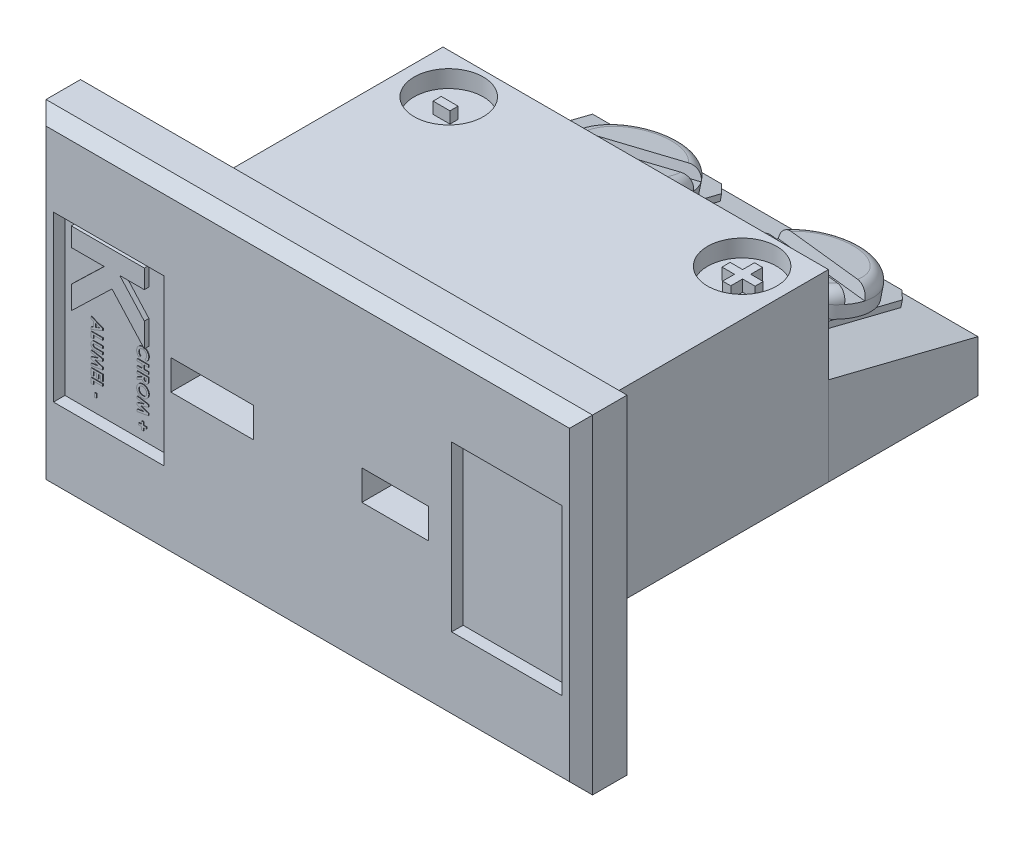
SolidWorks part; units mm, degrees
material "ABS PC"
ref_plane "Front" through (0, 0, 0) normal (0, 0, 1) x (1, 0, 0)
ref_plane "Top" through (0, 0, 0) normal (0, 1, 0) x (1, 0, 0)
ref_plane "Right" through (0, 0, 0) normal (1, 0, 0) x (0, 0, -1)
sketch "Sketch1" plane through (0, 0, 0) normal (0, 0, 1) x (1, 0, 0)
  line L0 (-24.3253, 0) -> (16.3539, 0) construction
  line L1 (-5.95, -0.65) -> (-2.35, -0.65)
  line L2 (-5.95, -0.65) -> (-5.95, 0.65)
  line L3 (-5.95, 0.65) -> (-2.35, 0.65)
  line L4 (-2.35, -0.65) -> (-2.35, 0.65)
  line L5 (2.35, -0.65) -> (5.25, -0.65)
  line L6 (2.35, -0.65) -> (2.35, 0.65)
  line L7 (2.35, 0.65) -> (5.25, 0.65)
  line L8 (5.25, -0.65) -> (5.25, 0.65)
  line L9 (-11.875, 7.15) -> (11.875, 7.15)
  line L10 (-11.875, 7.15) -> (-11.875, -7.15)
  line L11 (-11.875, -7.15) -> (11.875, -7.15)
  line L12 (11.875, 7.15) -> (11.875, -7.15)
  line L13 (0, 12.1646) -> (0, -12.5395) construction
  circle A0 centre (0, 0) radius 10.25 construction
  dimension "D1" = 20.5
  dimension "D2" = 0.65
  dimension "D3" = 1.3
  dimension "D4" = 0.65
  dimension "D5" = 1.3
  dimension "D6" = 2.9
  dimension "D7" = 3.6
  dimension "D8" = 4.7
  dimension "D9" = 2.35
  dimension "D10" = 23.75
  dimension "D11" = 14.3
extrude "Extrude1" add sketch "Sketch1" along normal blind 2
chamfer "Chamfer1" distance 0.5 angle 45 4 edges at (0, -7.15, 2) (11.875, 0, 2) (-11.875, 0, 2) (0, 7.15, 2)
sketch "Sketch2" plane through (0, 0, 2) normal (0, 0, 1) x (1, 0, 0)
  line L0 (-16.3854, 0) -> (14.9768, 0) construction
  line L9 (6.25, 3.575) -> (11.05, 3.575)
  line L10 (6.25, 3.575) -> (6.25, -3.575)
  line L11 (6.25, -3.575) -> (11.05, -3.575)
  line L12 (11.05, 3.575) -> (11.05, -3.575)
  line L13 (0, 8.3719) -> (0, -9.5694) construction
  line L14 (-6.25, -3.575) -> (-11.05, -3.575)
  line L15 (-11.05, 3.575) -> (-11.05, -3.575)
  line L16 (-6.25, 3.575) -> (-11.05, 3.575)
  line L17 (-6.25, 3.575) -> (-6.25, -3.575)
  dimension "D9" = 7.15
  dimension "D10" = 4.8
  dimension "D11" = 6.25
extrude "Cut-Extrude1" cut sketch "Sketch2" against normal blind 0.5
sketch "Sketch3" plane through (0, 0, 0) normal (0, 0, -1) x (-1, 0, 0)
  line L0 (-13.5325, 0) -> (13.4926, 0) construction
  line L1 (0, 8.4341) -> (0, -8.147) construction
  line L2 (-5.25, 0.65) -> (-2.35, 0.65) construction
  line L3 (-5.25, -0.65) -> (-2.35, -0.65)
  line L4 (-5.25, -0.65) -> (-5.25, 0.65)
  line L5 (-5.25, 0.65) -> (-2.35, 0.65)
  line L6 (-2.35, -0.65) -> (-2.35, 0.65)
  line L7 (2.35, -0.65) -> (5.95, -0.65)
  line L8 (2.35, -0.65) -> (2.35, 0.65)
  line L9 (2.35, 0.65) -> (5.95, 0.65)
  line L10 (5.95, -0.65) -> (5.95, 0.65)
  line L11 (-2.35, 0.65) -> (-2.35, -0.65) construction
  line L12 (-5.25, -0.65) -> (-5.25, 0.65) construction
  line L13 (-2.35, -0.65) -> (-5.25, -0.65) construction
  line L14 (2.35, 0.65) -> (5.95, 0.65) construction
  line L15 (5.95, -0.65) -> (2.35, -0.65) construction
  line L16 (2.35, -0.65) -> (2.35, 0.65) construction
  line L17 (5.95, 0.65) -> (5.95, -0.65) construction
  line L19 (-8.375, 4) -> (8.375, 4)
  line L20 (-8.375, 4) -> (-8.375, -4)
  line L21 (-8.375, -4) -> (8.375, -4)
  line L22 (8.375, 4) -> (8.375, -4)
  dimension "D1" = 16.75
  dimension "D2" = 8
extrude "Extrude2" add sketch "Sketch3" along normal blind 12.25
sketch "Sketch4" plane through (4.987, -4.5919, 1.5) normal (0, 0, 1) x (0, -1, 0)
  text T0 "<b>K</b>" font "Century Gothic" height in points 12
extrude "TC Type" add sketch "Sketch4" along normal blind 0.2
sketch "Sketch5" plane through (0, 0, 0) normal (0, 0, -1) x (-1, 0, 0)
  line L0 (5.95, 0.65) -> (5.95, -0.65) construction
  line L1 (5.95, -0.65) -> (2.35, -0.65) construction
  line L3 (-5.25, -0.65) -> (-2.35, -0.65)
  line L4 (-5.25, -0.65) -> (-5.25, -0.15)
  line L5 (-5.25, -0.15) -> (-2.35, -0.15)
  line L6 (-2.35, -0.65) -> (-2.35, -0.15)
  line L8 (2.35, -0.65) -> (5.95, -0.65)
  line L9 (2.35, -0.65) -> (2.35, -0.15)
  line L10 (2.35, -0.15) -> (5.95, -0.15)
  line L11 (5.95, -0.65) -> (5.95, -0.15)
  line L12 (2.35, -0.65) -> (2.35, 0.65) construction
  line L13 (-2.35, 0.65) -> (-2.35, -0.65) construction
  line L14 (-2.35, -0.65) -> (-5.25, -0.65) construction
  line L15 (-5.25, -0.65) -> (-5.25, 0.65) construction
  dimension "D2" = 0.5
  dimension "D3" = 0.5
extrude "Conatcts" add sketch "Sketch5" along normal up to surface (12.25 mm away) separate body up to face at (3.8, 0, -12.25)
sketch "Sketch6" plane through (0, 0, -12.25) normal (0, 0, -1) x (-1, 0, 0)
  line L0 (-8.375, -4) -> (8.375, -4)
  line L1 (-8.375, -0.15) -> (-5.25, -0.15)
  line L2 (-2.35, -0.15) -> (2.35, -0.15)
  line L3 (-5.25, -0.65) -> (-2.35, -0.65)
  line L4 (-5.25, -0.65) -> (-5.25, -0.15)
  line L5 (5.95, -0.15) -> (8.375, -0.15)
  line L6 (-2.35, -0.65) -> (-2.35, -0.15)
  line L7 (2.35, -0.65) -> (5.95, -0.65)
  line L8 (2.35, -0.65) -> (2.35, -0.15)
  line L9 (-2.35, -0.15) -> (-5.25, -0.15) construction
  line L10 (5.95, -0.65) -> (5.95, -0.15)
  line L11 (-5.25, -0.65) -> (-2.35, -0.65) construction
  line L12 (-2.35, -0.65) -> (-2.35, 0.65) construction
  line L13 (-5.25, 0.65) -> (-5.25, -0.65) construction
  line L14 (2.35, -0.65) -> (5.95, -0.65) construction
  line L15 (2.35, 0.65) -> (2.35, -0.65) construction
  line L16 (5.95, -0.65) -> (5.95, 0.65) construction
  line L17 (8.375, -4) -> (8.375, 4) construction
  line L18 (-8.375, 4) -> (-8.375, -4) construction
  line L19 (-8.375, -4) -> (8.375, -4) construction
  line L20 (-8.375, -0.15) -> (-8.375, -4)
  line L21 (8.375, -4) -> (8.375, -0.15)
extrude "Extrude5" add sketch "Sketch6" along normal blind 6.5 separate body
sketch "Sketch7" plane through (0, 0, 0) normal (1, 0, 0) x (0, 0, -1)
  line L1 (12.25, -0.15) -> (20.25, -0.15)
  line L2 (18.75, -0.15) -> (12.25, -0.15) construction
  line L3 (12.25, 4) -> (12.25, -4) construction
  line L4 (20.25, -0.15) -> (20.25, -2.15)
  line L6 (12.25, -0.15) -> (20.25, -2.15)
  dimension "D1" = 8
  dimension "D3" = 2
extrude "Cut-Extrude2" cut sketch "Sketch7" against normal through all and the other way through all
sketch "Sketch8" plane through (0, -0.65, 0) normal (0, 1, 0) x (-1, 0, 0)
  line L0 (-2.35, -12.25) -> (-5.25, -12.25) construction
  line L1 (-2.75, -14.25) -> (-4.75, -14.25)
  line L2 (-2.75, -14.25) -> (-2.75, -12.25)
  line L3 (3.15, -12.25) -> (5.15, -12.25)
  line L4 (-4.75, -14.25) -> (-4.75, -12.25)
  line L7 (5.15, -14.25) -> (3.15, -14.25)
  line L8 (5.15, -14.25) -> (5.15, -12.25)
  line L10 (3.15, -14.25) -> (3.15, -12.25)
  line L11 (-4.75, -12.25) -> (-2.75, -12.25)
  line L13 (0, 2.8444) -> (0, -22.9567) construction
  line L14 (2.35, -14.25) -> (5.95, -14.25) construction
  line L15 (-5.25, -14.25) -> (-2.35, -14.25) construction
  dimension "D1" = 2
  dimension "D2" = 2.75
  dimension "D5" = 2
  dimension "D6" = 3.15
extrude "Contact Extension" add sketch "Sketch8" along normal blind 0.2 and the other way blind 0.2
sketch "Sketch9" plane through (0, 2.7412, -0.6853) normal (0, 0.9701, -0.2425) x (-1, 0, 0)
  line L0 (-8.375, -18.6207) -> (8.375, -18.6207) construction
  line L1 (6.15, -13.9822) -> (2.15, -13.9822)
  line L2 (6.15, -13.9822) -> (6.15, -17.9207)
  line L3 (5.65, -18.4207) -> (2.65, -18.4207)
  line L4 (2.15, -13.9822) -> (2.15, -17.9207)
  line L5 (-1.8, -13.9822) -> (-5.8, -13.9822)
  line L6 (-1.8, -13.9822) -> (-1.8, -17.8207)
  line L7 (-2.3, -18.3207) -> (-5.3, -18.3207)
  line L8 (-5.8, -13.9822) -> (-5.8, -17.8207)
  line L9 (-5.3, -18.3207) -> (-5.8, -17.8207)
  line L10 (-1.8, -17.8207) -> (-2.3, -18.3207)
  line L11 (2.15, -17.9207) -> (2.65, -18.4207)
  line L12 (6.15, -17.9207) -> (5.65, -18.4207)
  line L13 (0, 4.2605) -> (0, -22.1998) construction
  line L15 (5.15, -13.9822) -> (5.95, -13.9822) construction
  point P1 (2.15, -18.4207)
  point P2 (6.15, -18.4207)
  point P5 (-5.8, -18.3207)
  point P6 (-1.8, -18.3207)
  dimension "D1" = 4
  dimension "D2" = 4
  dimension "D4" = 2.15
  dimension "D5" = 1.8
  dimension "D7" = 0.3
  dimension "D8" = 0.2
extrude "Contact Plate" add sketch "Sketch9" along normal blind 0.265 and the other way blind 0.265
sketch "Sketch10" plane through (0, 2.9983, -0.7496) normal (0, 0.9701, -0.2425) x (-1, 0, 0)
  line L0 (-4.75, -13.9337) -> (-2.75, -13.9337) construction
  line L1 (3.15, -13.9337) -> (5.15, -13.9337) construction
  circle A0 centre (-3.75, -15.7337) radius 2.25
  circle A1 centre (4.15, -15.7337) radius 2.25
  dimension "D3" = 4.5
  dimension "D4" = 4.5
  dimension "D1" = 1.8
  dimension "D2" = 1.8
extrude "Screw Head" add sketch "Sketch10" along normal blind 1
fillet "Fillet1" radius 0.5 2 edges at (-4.15, 0.6981, -14.0732) (3.75, 0.6981, -14.0732)
sketch "Sketch11" plane through (0, 3.9684, -0.9921) normal (0, 0.9701, -0.2425) x (-1, 0, 0)
  line L0 (-8.0045, -15.5148) -> (-0.016, -16.6848)
  line L1 (-7.9993, -14.7071) -> (-0.0126, -15.8768)
  line L2 (-8.0045, -15.5148) -> (-7.9993, -14.7071)
  line L3 (-0.016, -16.6848) -> (-0.0126, -15.8768)
  line L4 (1.3508, -16.6848) -> (7.8329, -13.4469)
  line L5 (1.7083, -17.4005) -> (8.1282, -14.1936)
  line L6 (8.1282, -14.1936) -> (7.8329, -13.4469)
  line L8 (1.7083, -17.4005) -> (1.3508, -16.6848)
  circle A0 centre (-3.75, -15.7337) radius 1.75 construction
  circle A1 centre (4.15, -15.7337) radius 1.75 construction
  dimension "D1" = 0.4
  dimension "D2" = 0.4
  dimension "D3" = 0.4
  dimension "D4" = 0.4
extrude "Screw Slot" cut sketch "Sketch11" against normal blind 0.5
sketch "Sketch12" plane through (0, 2.7061, -0.8256) normal (0, -0.9701, 0.2425) x (1, 0, 0)
  circle A0 centre (3.75, -15.5891) radius 1.25
  circle A1 centre (-4.15, -15.5891) radius 1.25
  arc A2 (-2.15, -16.6199) -> (-2.15, -14.5583) centre (-4.15, -15.5891) ccw construction
  arc A3 (5.8, -16.5165) -> (5.8, -14.6617) centre (3.75, -15.5891) ccw construction
  dimension "D1" = 2.5
  dimension "D2" = 2.5
extrude "Screw" add sketch "Sketch12" along normal blind 3.5 separate body
sketch "Sketch13" plane through (0, 4, 0) normal (0, 1, 0) x (1, 0, 0)
  line L0 (0, 19.4175) -> (0, -3.6972) construction
  line L1 (-8.375, 12.25) -> (8.375, 12.25) construction
  line L2 (8.375, 12.25) -> (8.375, 0) construction
  circle A0 centre (6.375, 10.5) radius 1.5
  circle A1 centre (-6.375, 10.5) radius 1.5
  dimension "D1" = 3
  dimension "D3" = 2
  dimension "D2" = 1.75
extrude "Cut-Extrude4" cut sketch "Sketch13" against normal blind 0.75
sketch "Sketch15" plane through (0, 3.25, 0) normal (0, 1, 0) x (1, 0, 0)
  text T0 "<b>+</b>" font "Century Gothic" height in points 8
  point P0 (5.5568, 9.4402)
extrude "Positive" add sketch "Sketch15" along normal blind 0.5
sketch "Sketch16" plane through (0, 3.25, 0) normal (0, 1, 0) x (1, 0, 0)
  text T0 "<b>-</b>" font "Century Gothic" height in points 8
  point P0 (-7.048, 9.6532)
extrude "Negative" add sketch "Sketch16" along normal blind 0.5
sketch "Sketch17" plane through (0, 0, 1.5) normal (0, 0, 1) x (1, 0, 0)
  line L0 (-7.8969, 0) -> (-7.8969, -3.3667) construction
  line L1 (-9.8848, 0) -> (-9.8848, -3.3667) construction
  text T0 "<b>CHROM +</b>" font "Century Gothic" height 0.5
  text T1 "<b>ALUMEL -</b>" font "Century Gothic" height 0.5
extrude "Teminal Info" add sketch "Sketch17" along normal blind 0.025 separate body
sketch "Sketch18" plane through (0, 4, 0) normal (0, 1, 0) x (1, 0, 0)
  line L0 (11.875, 0) -> (-11.875, 0) construction
  line L1 (-8.375, 0) -> (8.375, 0)
  line L2 (-8.375, 0) -> (-8.375, 0.25)
  line L3 (-8.375, 0.25) -> (8.375, 0.25)
  line L4 (8.375, 0) -> (8.375, 0.25)
  line L5 (-8.375, 0) -> (8.375, 0) construction
  line L6 (8.375, 12.25) -> (8.375, 0) construction
  line L7 (-8.375, 12.25) -> (-8.375, 0) construction
  dimension "D1" = 0.25
extrude "Mounting Slot" cut sketch "Sketch18" against normal blind 3.75
